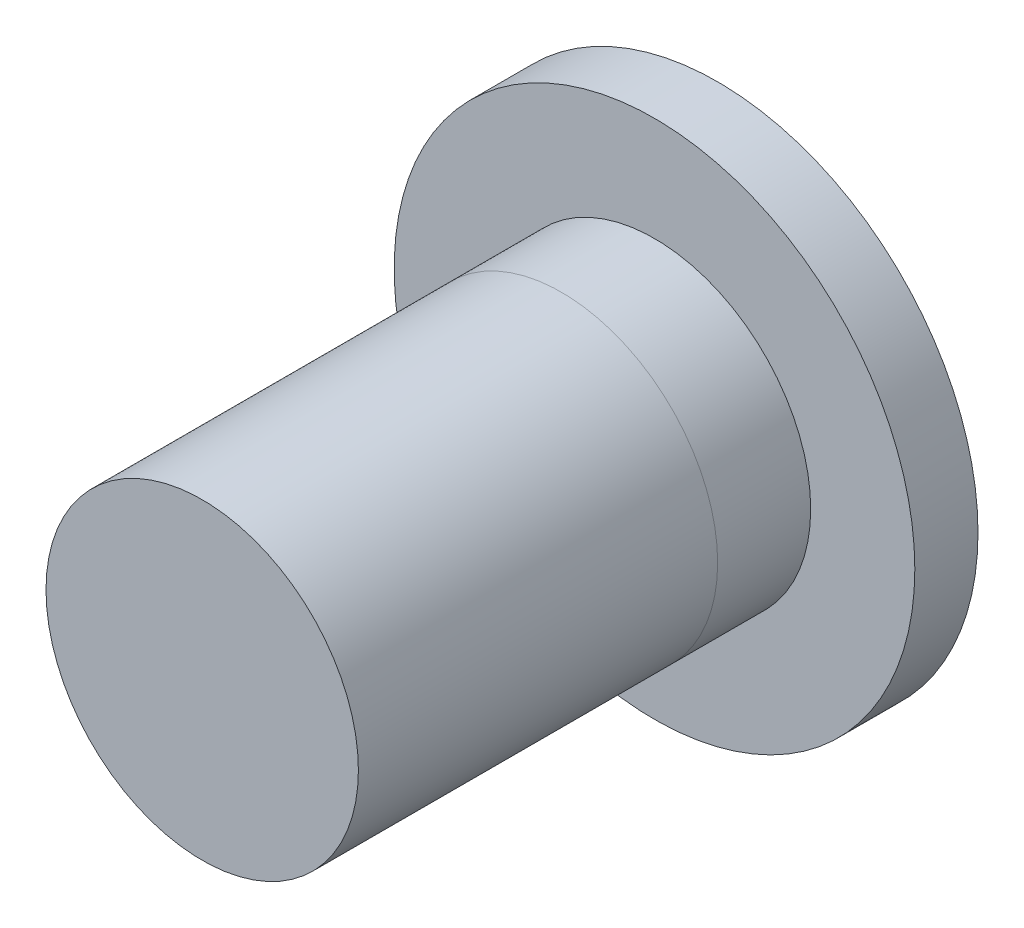
SolidWorks part; units mm, degrees
ref_plane "Front Plane" through (0, 0, 0) normal (0, 0, 1) x (1, 0, 0)
ref_plane "Top Plane" through (0, 0, 0) normal (0, 1, 0) x (1, 0, 0)
ref_plane "Right Plane" through (0, 0, 0) normal (1, 0, 0) x (0, 0, -1)
ref_plane "Plane1" through (0, 0, 1) normal (0, 0, 1) x (1, 0, 0)
sketch "Sketch1" plane through (0, 0, 1) normal (0, 0, 1) x (1, 0, 0)
  circle A2 centre (-18.768, 46) radius 10
  circle A6 centre (-18.768, 46) radius 4.5
extrude "Boss-Extrude1" add sketch "Sketch1" along normal up to surface (2.7764 mm away)
sketch "Sketch2" plane through (0, 0, 3.7764) normal (0, 0, 1) x (1, 0, 0)
  circle A0 centre (-18.768, 46) radius 4.5 construction
  circle A1 centre (-18.768, 46) radius 4.5
  circle A2 centre (-18.768, 46) radius 6
extrude "Boss-Extrude3" add sketch "Sketch2" along normal up to surface (3.2236 mm away)
sketch "Sketch3" plane through (0, 0, 7) normal (0, 0, 1) x (1, 0, 0)
  circle A1 centre (-18.768, 46) radius 6 construction
  circle A3 centre (-18.768, 46) radius 3.5
  circle A4 centre (-18.768, 46) radius 6
extrude "Boss-Extrude4" add sketch "Sketch3" along normal offset from surface (3.45 mm away) 0.25 offset beyond the face yes
sketch "Sketch4" plane through (0, 0, 10.45) normal (0, 0, 1) x (1, 0, 0)
  line L1 (-17.1006, 49.0773) -> (-17.1006, 42.9227)
  arc A1 (-17.1006, 49.0773) -> (-17.1006, 42.9227) centre (-18.768, 46) ccw
  circle A2 centre (-18.768, 46) radius 6 construction
  circle A3 centre (-18.768, 46) radius 6
extrude "Boss-Extrude5" add sketch "Sketch4" along normal up to surface (9.75 mm away)
sketch "Sketch5" plane through (0, 0, 20.2) normal (0, 0, 1) x (1, 0, 0)
  circle A0 centre (-18.768, 46) radius 6 construction
  circle A1 centre (-18.768, 46) radius 6
extrude "Boss-Extrude6" add sketch "Sketch5" along normal blind 0.6
sketch "Sketch6" plane through (0, 0, 3.7764) normal (0, 0, 1) x (1, 0, 0)
  circle A0 centre (-18.768, 46) radius 6 construction
  circle A1 centre (-18.768, 46) radius 10
  circle A2 centre (-18.768, 46) radius 10
  circle A3 centre (-18.768, 46) radius 6
  dimension "D1" = 0
extrude "Cut-Extrude1" cut sketch "Sketch6" against normal blind 0.35 body kept at (-8.768, 46, 1)
